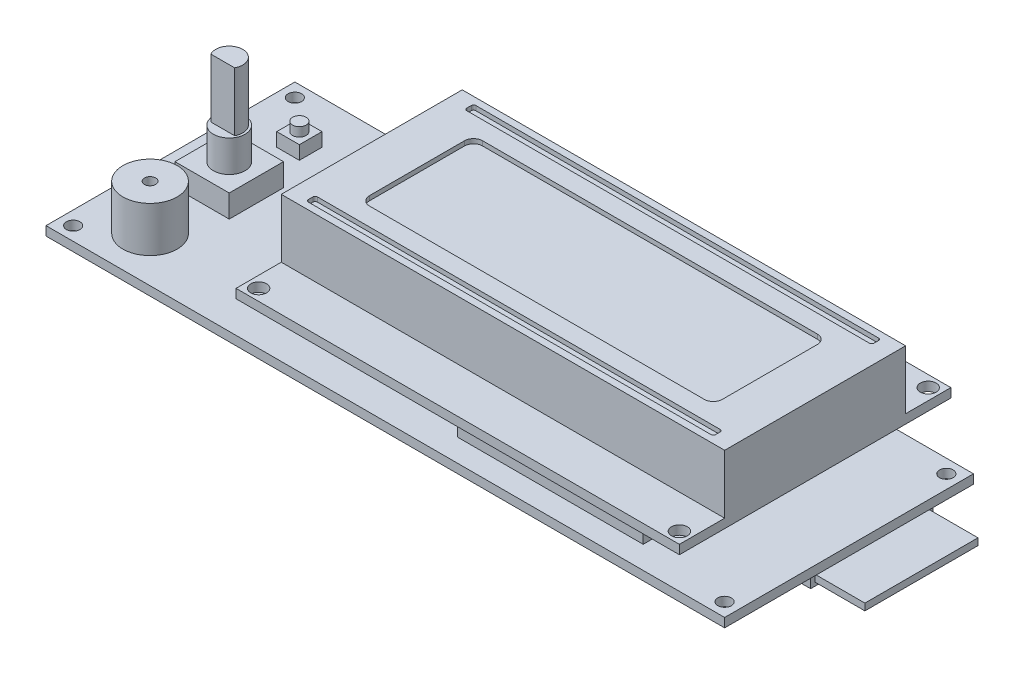
SolidWorks part; units mm, degrees
ref_plane "Front Plane" through (0, 0, 0) normal (0, 0, 1) x (1, 0, 0)
ref_plane "Top Plane" through (0, 0, 0) normal (0, 1, 0) x (1, 0, 0)
ref_plane "Right Plane" through (0, 0, 0) normal (1, 0, 0) x (0, 0, -1)
sketch "Sketch1" plane through (0, 0, 0) normal (0, 1, 0) x (1, 0, 0)
  line L0 (75, 55) -> (75, 0) construction
  line L1 (0, 0) -> (150, 0)
  line L2 (0, 0) -> (0, 55)
  line L3 (0, 55) -> (150, 55)
  line L4 (150, 0) -> (150, 55)
  line L5 (0, 27.5) -> (150, 27.5) construction
  circle A0 centre (3, 52) radius 1.5
  circle A1 centre (147, 52) radius 1.5
  circle A2 centre (147, 3) radius 1.5
  circle A3 centre (3, 3) radius 1.5
  dimension "D3" = 3
  dimension "D1" = 55
  dimension "D2" = 150
  dimension "D4" = 3
  dimension "D5" = 3
extrude "Boss-Extrude1" add sketch "Sketch1" along normal blind 2
sketch "Sketch2" plane through (0, 2, 0) normal (0, 1, 0) x (1, 0, 0)
  line L0 (0, 0) -> (150, 0) construction
  line L1 (0, 0) -> (0, 55) construction
  circle A0 centre (13, 10) radius 6
  dimension "D1" = 12
  dimension "D2" = 10
  dimension "D3" = 13
extrude "Boss-Extrude2" add sketch "Sketch2" along normal blind 10
sketch "Sketch3" plane through (0, 2, 0) normal (0, 1, 0) x (1, 0, 0)
  line L0 (0, 27.5) -> (150, 27.5) construction
  line L1 (7, 33.5) -> (19, 33.5)
  line L2 (7, 33.5) -> (7, 21.5)
  line L3 (7, 21.5) -> (19, 21.5)
  line L4 (19, 33.5) -> (19, 21.5)
  line L5 (13, 0) -> (13, 55) construction
  line L6 (0, 0) -> (150, 0) construction
  line L7 (0, 55) -> (150, 55) construction
  line L8 (7, 27.5) -> (19, 27.5) construction
  circle A1 centre (13, 10) radius 6 construction
  point P4 (7, 27.5)
  point P16 (13, 27.5)
  point P19 (13, 16)
  dimension "D1" = 12
  dimension "D2" = 12
extrude "Boss-Extrude3" add sketch "Sketch3" along normal blind 25
sketch "Sketch4" plane through (0, 2, 0) normal (0, 1, 0) x (1, 0, 0)
  line L0 (13, 45.5) -> (13, 40.5) construction
  line L1 (10.5, 45.5) -> (15.5, 45.5)
  line L2 (10.5, 45.5) -> (10.5, 40.5)
  line L3 (10.5, 40.5) -> (15.5, 40.5)
  line L4 (15.5, 45.5) -> (15.5, 40.5)
  line L5 (10.5, 43) -> (15.5, 43) construction
  line L7 (13, 0) -> (13, 55) construction
  line L8 (7, 33.5) -> (19, 33.5) construction
  line L9 (150, 0) -> (150, 55) construction
  line L10 (127, 8) -> (86, 8)
  line L11 (127, 8) -> (127, 5)
  line L12 (127, 5) -> (86, 5)
  line L13 (86, 8) -> (86, 5)
  line L14 (0, 0) -> (150, 0) construction
  point P8 (13, 43)
  dimension "D1" = 5
  dimension "D2" = 5
  dimension "D3" = 7
  dimension "D4" = 23
  dimension "D5" = 41
  dimension "D6" = 3
  dimension "D7" = 5
extrude "Boss-Extrude4" add sketch "Sketch4" along normal blind 5
sketch "Sketch5" plane through (0, 7, 0) normal (0, 1, 0) x (1, 0, 0)
  line L0 (86, 5) -> (127, 5) construction
  line L1 (86, 8) -> (127, 8)
  line L2 (86, 8) -> (86, 5)
  line L3 (86, 5) -> (127, 5)
  line L4 (127, 8) -> (127, 5)
  line L5 (86, 5) -> (127, 5) construction
  line L6 (10.5, 43) -> (15.5, 43) construction
  line L7 (10.5, 45.5) -> (10.5, 40.5) construction
  line L8 (15.5, 40.5) -> (15.5, 45.5) construction
  line L10 (10.5, 45.5) -> (15.5, 45.5)
  line L11 (10.5, 45.5) -> (10.5, 40.5)
  line L12 (10.5, 40.5) -> (15.5, 40.5)
  line L13 (15.5, 45.5) -> (15.5, 40.5)
  circle A0 centre (13, 43) radius 1.5
  point P15 (13, 43)
  dimension "D1" = 3
extrude "Cut-Extrude1" cut sketch "Sketch5" against normal blind 2
sketch "Sketch6" plane through (0, 27, 0) normal (0, 1, 0) x (1, 0, 0)
  line L0 (10.3706, 26.0556) -> (15.6294, 26.0556)
  line L1 (7, 33.5) -> (19, 33.5)
  line L2 (7, 33.5) -> (7, 21.5)
  line L3 (7, 21.5) -> (19, 21.5)
  line L4 (19, 33.5) -> (19, 21.5)
  arc A0 (15.6294, 26.0556) -> (10.3706, 26.0556) centre (13, 27.5) ccw
  dimension "D1" = 6
extrude "Cut-Extrude2" cut sketch "Sketch6" against normal blind 13
sketch "Sketch7" plane through (0, 14, 0) normal (0, 1, 0) x (1, 0, 0)
  line L1 (7, 33.5) -> (19, 33.5)
  line L2 (7, 33.5) -> (7, 21.5)
  line L3 (7, 21.5) -> (19, 21.5)
  line L4 (19, 33.5) -> (19, 21.5)
  circle A0 centre (13, 27.5) radius 3.5
  line M4 (7, 33.5) -> (7, 21.5)
  line M5 (7, 21.5) -> (19, 21.5)
  line M6 (19, 21.5) -> (19, 33.5)
  line M7 (19, 33.5) -> (7, 33.5)
  dimension "D1" = 7
extrude "Cut-Extrude3" cut sketch "Sketch7" against normal blind 7 contours A0 M7 M4 M5 M6 region at (13, 14, -33.3303)
sketch "Sketch8" plane through (0, 12, 0) normal (0, 1, 0) x (1, 0, 0)
  circle A0 centre (13, 10) radius 1.25
  point P0 (13, 10)
  dimension "D1" = 2.5
extrude "Cut-Extrude4" cut sketch "Sketch8" against normal blind 5
sketch "Sketch9" plane through (0, 0, 0) normal (0, -1, 0) x (1, 0, 0)
  line L0 (0, -55) -> (150, -55) construction
  line L1 (149, -20) -> (131, -20)
  line L2 (149, -20) -> (149, -47)
  line L3 (149, -47) -> (124, -47)
  line L4 (124, -22) -> (124, -47)
  line L5 (150, 0) -> (150, -55) construction
  line L6 (124, -22) -> (129, -22)
  line L7 (129, -22) -> (131, -20)
  dimension "D1" = 8
  dimension "D2" = 27
  dimension "D3" = 1
  dimension "D4" = 25
  dimension "D5" = 2
  dimension "D6" = 5
  dimension "D7" = 45
extrude "Boss-Extrude5" add sketch "Sketch9" along normal blind 3
sketch "Sketch10" plane through (149, 0, 0) normal (1, 0, 0) x (0, 0, -1)
  line L0 (20, -1.5) -> (47, -1.5) construction
  line L1 (20, -3) -> (20, 0) construction
  line L2 (47, -3) -> (47, 0) construction
  line L3 (33.5, -3) -> (33.5, 0) construction
  line L4 (47, -3) -> (20, -3) construction
  line L5 (0, 0) -> (55, 0) construction
  line L6 (33.5, -2.25) -> (33.5, -0.75) construction
  line L7 (21, -2.25) -> (46, -2.25)
  line L8 (21, -2.25) -> (21, -0.75)
  line L9 (21, -0.75) -> (46, -0.75)
  line L10 (46, -2.25) -> (46, -0.75)
  line L11 (21, -1.5) -> (46, -1.5) construction
  point P20 (33.5, -1.5)
  point P21 (33.5, -1.5)
  dimension "D1" = 1.5
  dimension "D2" = 25
extrude "Cut-Extrude5" cut sketch "Sketch10" against normal blind 18
sketch "Sketch11" plane through (0, 5, 0) normal (0, 1, 0) x (1, 0, 0)
  line L0 (0, 0) -> (150, 0) construction
  line L1 (136, 64) -> (38, 64)
  line L2 (136, 64) -> (136, 4)
  line L3 (136, 4) -> (38, 4)
  line L4 (38, 64) -> (38, 4)
  line L5 (150, 0) -> (150, 55) construction
  line L6 (87, 64) -> (87, 4) construction
  line L7 (38, 34) -> (136, 34) construction
  circle A0 centre (40.5, 61.5) radius 1.75
  circle A1 centre (133.5, 61.5) radius 1.75
  circle A2 centre (133.5, 6.5) radius 1.75
  circle A3 centre (40.5, 6.5) radius 1.75
  point P12 (87, 34)
  dimension "D5" = 3.5
  dimension "D1" = 98
  dimension "D2" = 60
  dimension "D3" = 4
  dimension "D4" = 14
  dimension "D6" = 2.5
  dimension "D7" = 2.5
extrude "Boss-Extrude6" add sketch "Sketch11" along normal blind 2
sketch "Sketch12" plane through (0, 7, 0) normal (0, 1, 0) x (1, 0, 0)
  line L0 (38, 34) -> (136, 34) construction
  line L1 (38, 54) -> (136, 54)
  line L2 (38, 54) -> (38, 14)
  line L3 (38, 14) -> (136, 14)
  line L4 (136, 54) -> (136, 14)
  dimension "D1" = 40
extrude "Boss-Extrude7" add sketch "Sketch12" along normal blind 13
sketch "Sketch13" plane through (0, 20, 0) normal (0, 1, 0) x (1, 0, 0)
  line L0 (87, 54) -> (87, 14) construction
  line L1 (136, 54) -> (38, 54) construction
  line L2 (38, 14) -> (136, 14) construction
  line L3 (38, 34) -> (136, 34) construction
  line L4 (38, 54) -> (38, 14) construction
  line L5 (136, 14) -> (136, 54) construction
  line L6 (87, 46.5) -> (87, 21.5) construction
  line L7 (50, 46.5) -> (124, 46.5)
  line L8 (48, 44.5) -> (48, 23.5)
  line L9 (50, 21.5) -> (124, 21.5)
  line L10 (126, 44.5) -> (126, 23.5)
  line L11 (87, 52.5) -> (87, 50.5) construction
  line L12 (42.5, 52.5) -> (131.5, 52.5)
  line L13 (42, 52) -> (42, 51)
  line L14 (42.5, 50.5) -> (131.5, 50.5)
  line L15 (132, 52) -> (132, 51)
  line L16 (136, 54) -> (38, 54) construction
  line L17 (42, 52.5) -> (42, 50.5)
  line L18 (132, 52.5) -> (132, 50.5)
  line L19 (87, 15.5) -> (87, 17.5) construction
  line L20 (132, 16) -> (132, 17)
  line L21 (42, 16) -> (42, 17)
  line L22 (132, 15.5) -> (132, 17.5)
  line L23 (42.5, 17.5) -> (131.5, 17.5)
  line L24 (42, 15.5) -> (42, 17.5)
  line L25 (42.5, 15.5) -> (131.5, 15.5)
  arc A0 (131.5, 50.5) -> (132, 51) centre (131.5, 51) ccw
  arc A1 (131.5, 52.5) -> (132, 52) centre (131.5, 52) cw
  arc A2 (42, 51) -> (42.5, 50.5) centre (42.5, 51) ccw
  arc A3 (42.5, 52.5) -> (42, 52) centre (42.5, 52) ccw
  arc A4 (131.5, 15.5) -> (132, 16) centre (131.5, 16) ccw
  arc A5 (131.5, 17.5) -> (132, 17) centre (131.5, 17) cw
  arc A6 (42.5, 15.5) -> (42, 16) centre (42.5, 16) cw
  arc A7 (42.5, 17.5) -> (42, 17) centre (42.5, 17) ccw
  arc A8 (124, 46.5) -> (126, 44.5) centre (124, 44.5) cw
  arc A9 (48, 23.5) -> (50, 21.5) centre (50, 23.5) ccw
  arc A10 (50, 46.5) -> (48, 44.5) centre (50, 44.5) ccw
  arc A11 (124, 21.5) -> (126, 23.5) centre (124, 23.5) ccw
  point P18 (87, 34)
  point P19 (87, 34)
  point P62 (48, 21.5)
  point P65 (48, 46.5)
  dimension "D6" = 0.5
  dimension "D7" = 0.5
  dimension "D8" = 2
  dimension "D1" = 25
  dimension "D2" = 10
  dimension "D3" = 4
  dimension "D4" = 1.5
  dimension "D5" = 2
extrude "Cut-Extrude6" cut sketch "Sketch13" against normal blind 1 contours L15 L12 L13 L14 | L10 L7 L8 L9 | L21 L25 L20 L23 region at (87, 20, -34) region at (87, 20, -51.5) region at (87, 20, -16.5)
sketch "Sketch14" plane through (131, 0, 0) normal (1, 0, 0) x (0, 0, -1)
  line L1 (21, -0.75) -> (46, -0.75)
  line L2 (21, -0.75) -> (21, -2.25)
  line L3 (21, -2.25) -> (46, -2.25)
  line L4 (46, -0.75) -> (46, -2.25)
extrude "Boss-Extrude8" add sketch "Sketch14" along normal offset from surface (29 mm away) 11 up to face at (149, -1.5, -33.5) offset beyond the face yes
